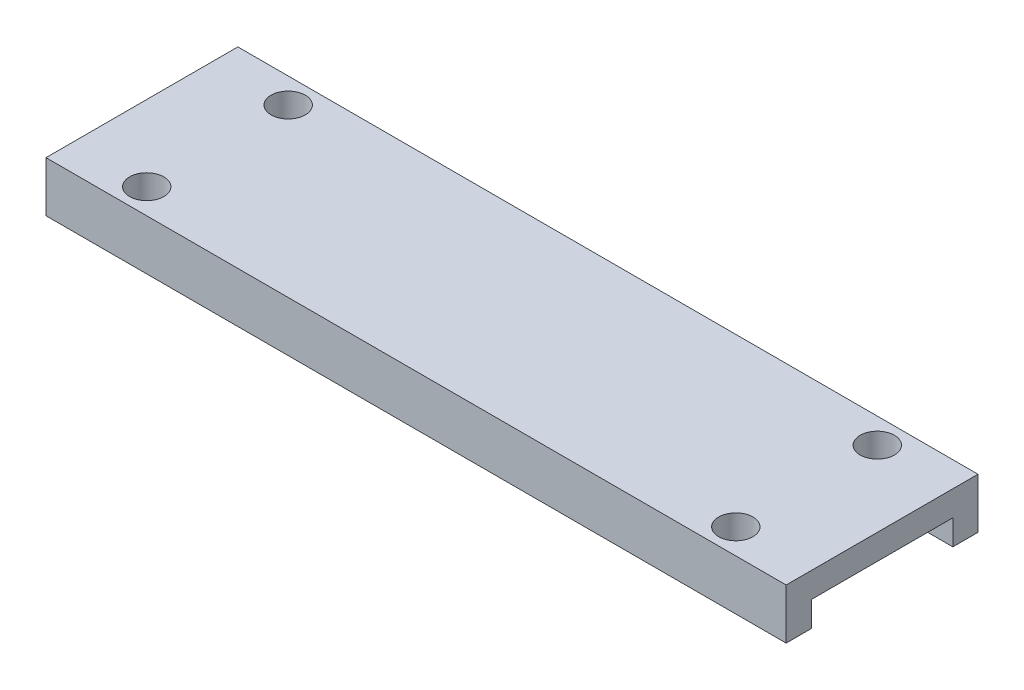
SolidWorks part; units mm, degrees
material "1060 Alloy"
ref_plane "Front Plane" through (0, 0, 0) normal (0, 0, 1) x (1, 0, 0)
ref_plane "Top Plane" through (0, 0, 0) normal (0, 1, 0) x (1, 0, 0)
ref_plane "Right Plane" through (0, 0, 0) normal (1, 0, 0) x (0, 0, -1)
sketch "Sketch1" plane through (0, 0, 0) normal (0, 1, 0) x (1, 0, 0)
  line L1 (-73.5, -19.05) -> (73.5, -19.05)
  line L2 (-73.5, -19.05) -> (-73.5, 19.05)
  line L3 (-73.5, 19.05) -> (73.5, 19.05)
  line L4 (73.5, -19.05) -> (73.5, 19.05)
  line L5 (-73.5, -19.05) -> (73.5, 19.05) construction
  line L6 (-73.5, 19.05) -> (73.5, -19.05) construction
  point P0 (0, 0)
  dimension "D1" = 147
  dimension "D2" = 38.1
extrude "Boss-Extrude1" add sketch "Sketch1" along normal mid plane 10
sketch "Sketch2" plane through (0, 0, 0) normal (1, 0, 0) x (0, 0, -1)
  line L0 (-14.05, 0) -> (14.05, 0)
  line L1 (14.05, 0) -> (14.05, -5)
  line L2 (-19.05, -5) -> (19.05, -5) construction
  line L3 (-14.05, -5) -> (-14.05, 0)
  line L4 (-19.05, 5) -> (-19.05, -5) construction
  line L5 (-14.05, -5) -> (14.05, -5)
  dimension "D1" = 5
extrude "Cut-Extrude1" cut sketch "Sketch2" against normal through all both and the other way through all
hole_wizard "Tap Drill for M8x1.25 Tap1" positions "Sketch4" profile "Sketch3" hole size "M8x1.25" standard "ANSI Metric"
sketch "Sketch4" plane through (0, 5, 0) normal (0, 1, 0) x (1, 0, 0)
  line L2 (73.5, 19.05) -> (-73.5, 19.05) construction
  line L3 (-73.5, 19.05) -> (-73.5, -19.05) construction
  line L4 (-73.5, -19.05) -> (73.5, -19.05) construction
  line L5 (73.5, -19.05) -> (73.5, 19.05) construction
  point P0 (-58.5, 14.05)
  point P2 (58.5, 14.05)
  point P4 (58.5, -14.05)
  point P6 (-58.5, -14.05)
  dimension "D1" = 5
  dimension "D2" = 15
  dimension "D3" = 15
  dimension "D4" = 5
  dimension "D5" = 5
  dimension "D6" = 15
  dimension "D7" = 15
  dimension "D8" = 5
sketch "Sketch3" plane through (-58.5, 5, -14.05) normal (1, 0, 0) x (0, 0, 1)
  line L0 (0, 0) -> (0, 14.0429)
  line L1 (0, 14.0429) -> (3.4, 12)
  line L2 (3.4, 12) -> (3.4, 0)
  line L5 (3.4, 0) -> (0, 0)
  line L10 (0, 14.0429) -> (-3.4, 12) construction
  line L11 (0, -6.35) -> (0, 107.95) construction
  dimension "Hole Dia." = 6.8
  dimension "Hole Depth" = 12
  dimension "Drill Angle" = 118
cosmetic thread "Cosmetic Thread1" parameters "D2"=8
cosmetic thread "Cosmetic Thread2" parameters "D2"=8
cosmetic thread "Cosmetic Thread3" parameters "D2"=8
cosmetic thread "Cosmetic Thread4" parameters "D2"=8
sketch "Sketch5" plane through (0, 0, 0) normal (0, -1, 0) x (1, 0, 0)
  line L0 (-73.5, 14.05) -> (-61.9, 14.05) construction
  line L1 (-64.4, 14.05) -> (-61.9, 14.05)
  line L2 (-55.1, 14.05) -> (-52.6, 14.05)
  line L4 (-73.5, -14.05) -> (-61.9, -14.05) construction
  line L5 (-55.1, -14.05) -> (55.1, -14.05) construction
  line L6 (-64.4, -14.05) -> (-61.9, -14.05)
  line L7 (-55.1, -14.05) -> (-52.6, -14.05)
  line L8 (52.6, -14.05) -> (55.1, -14.05)
  line L9 (61.9, -14.05) -> (64.4, -14.05)
  line L10 (-55.1, 14.05) -> (55.1, 14.05) construction
  line L11 (61.9, 14.05) -> (73.5, 14.05) construction
  line L12 (52.6, 14.05) -> (55.1, 14.05)
  line L13 (61.9, 14.05) -> (64.4, 14.05)
  arc A0 (-61.9, 14.05) -> (-55.1, 14.05) centre (-58.5, 14.05) ccw
  arc A1 (-64.4, 14.05) -> (-52.6, 14.05) centre (-58.5, 14.05) ccw
  arc A2 (-61.9, -14.05) -> (-55.1, -14.05) centre (-58.5, -14.05) cw
  arc A3 (-64.4, -14.05) -> (-52.6, -14.05) centre (-58.5, -14.05) cw
  arc A4 (55.1, -14.05) -> (61.9, -14.05) centre (58.5, -14.05) cw
  arc A5 (52.6, -14.05) -> (64.4, -14.05) centre (58.5, -14.05) cw
  arc A6 (55.1, 14.05) -> (61.9, 14.05) centre (58.5, 14.05) ccw
  arc A7 (52.6, 14.05) -> (64.4, 14.05) centre (58.5, 14.05) ccw
  dimension "D1" = 3.4
  dimension "D2" = 2.5
  dimension "D3" = 3.4
  dimension "D4" = 2.5
  dimension "D5" = 3.4
  dimension "D6" = 2.5
  dimension "D7" = 3.4
  dimension "D8" = 2.5
extrude "Boss-Extrude2" add sketch "Sketch5" along normal up to surface (5 mm away) up to face at (0, -5, 16.15)
